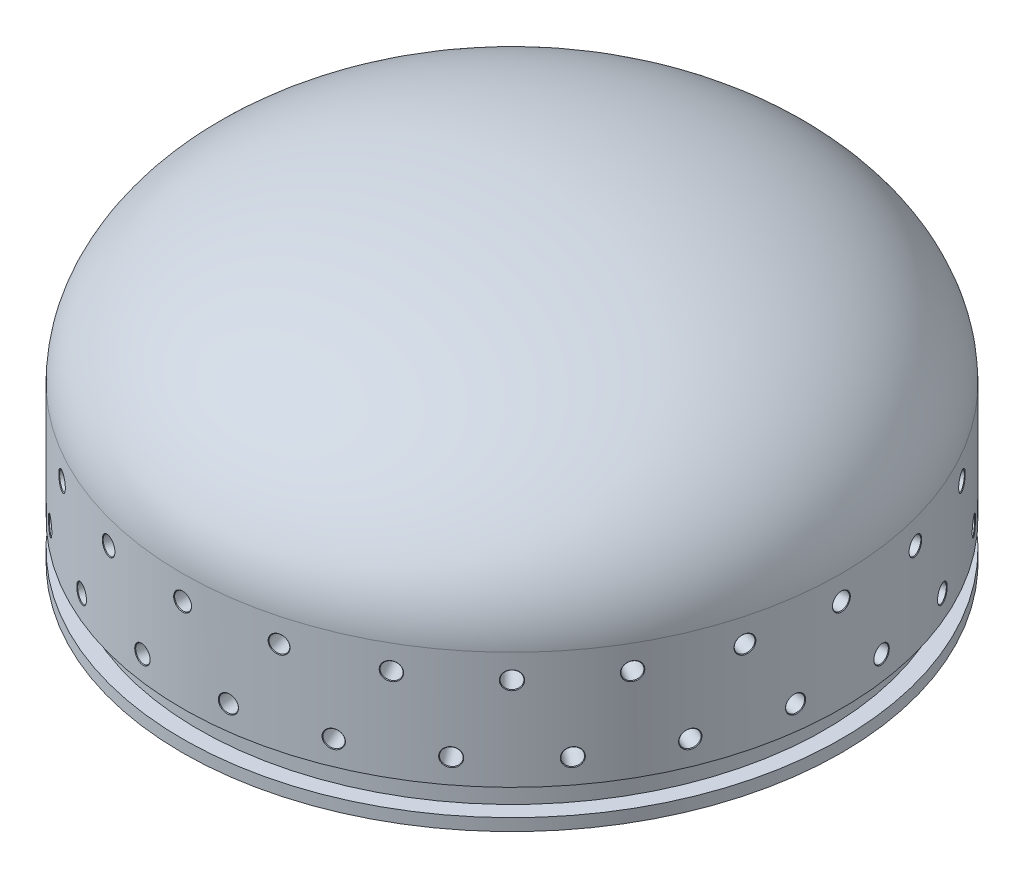
SolidWorks part; units mm, degrees
material "AW-6082-T6 (PA4)"
ref_plane "Płaszczyzna przednia" through (0, 0, 0) normal (0, 0, 1) x (1, 0, 0)
ref_plane "Płaszczyzna górna" through (0, 0, 0) normal (0, 1, 0) x (1, 0, 0)
ref_plane "Płaszczyzna prawa" through (0, 0, 0) normal (1, 0, 0) x (0, 0, -1)
sketch "Szkic1" plane through (0, 0, 0) normal (0, 1, 0) x (1, 0, 0)
  circle A0 centre (0, 0) radius 81.7
  dimension "D1" = 163.4
extrude "Dodanie-wyciągnięcie1" add sketch "Szkic1" along normal blind 38.5
ref_plane "Płaszczyzna1" through (0, 0, -81.7) normal (0, 0, -1) x (-1, 0, 0)
ref_plane "Płaszczyzna2" through (10.664, 0, -81.001) normal (0.1305, 0, -0.9914) x (0, -1, 0)
hole_wizard "Otwór gwintowany M51" positions "Szkic2" profile "Szkic3" hole size "M5" standard "ISO"
sketch "Szkic2" plane through (0, 0, -81.7) normal (0, 0, -1) x (-1, 0, 0)
  line L0 (81.7, 0) -> (81.7, 38.5) construction
  line L1 (-81.7, 38.5) -> (-81.7, 0) construction
  line L2 (81.7, 0) -> (81.7, 38.5)
  line L3 (-81.7, 38.5) -> (-81.7, 0)
  line L4 (0, 51.4702) -> (0, -13.4001) construction
  line L5 (81.7, 38.5) -> (-81.7, 38.5) construction
  point P11 (0, 32.5)
  dimension "D1" = 6
sketch "Szkic3" plane through (0, 32.5, -81.7) normal (1, 0, 0) x (0, 1, 0)
  line L0 (0, 0) -> (0, 9.2618)
  line L1 (0, 9.2618) -> (2.1, 8)
  line L2 (2.1, 8) -> (2.1, 0.15)
  line L3 (2.1, 0.15) -> (2.25, 0)
  line L5 (2.25, 0) -> (0, 0)
  line L6 (-2.1, 0.15) -> (-2.25, 0) construction
  line L10 (0, 9.2618) -> (-2.1, 8) construction
  line L11 (0, -6.35) -> (0, 107.95) construction
  dimension "Średnica otworu" = 4.2
  dimension "Głębokośc otworu" = 8
  dimension "Średnica zewnętrznego pogłębienia stożkowego" = 4.5
  dimension "Kąt zewnętrznego pogłębienia stożkowego" = 90
  dimension "Kąt wiertła" = 118
hole_wizard "Otwór gwintowany M52" positions "Szkic6" profile "Szkic7" hole size "M5" standard "ISO"
sketch "Szkic6" plane through (10.664, 0, -81.001) normal (0.1305, 0, -0.9914) x (0, -1, 0)
  line L0 (-38.5, -81.7) -> (0, -81.7) construction
  line L1 (0, 81.7) -> (-38.5, 81.7) construction
  line L2 (-38.5, -81.7) -> (0, -81.7)
  line L3 (0, 81.7) -> (-38.5, 81.7)
  line L4 (-54.6249, 0) -> (16.9218, 0) construction
  ellipse E0 centre (-32.5, 10.6444) end of major axis (-30.4, 10.6444) minor radius 2.082 construction
  point P10 (-15.5, 0)
  dimension "D1" = 17
sketch "Szkic7" plane through (10.664, 15.5, -81.001) normal (0, 1, 0) x (-0.9914, 0, -0.1305)
  line L0 (0, 0) -> (0, 9.2618)
  line L1 (0, 9.2618) -> (2.1, 8)
  line L2 (2.1, 8) -> (2.1, 0.15)
  line L3 (2.1, 0.15) -> (2.25, 0)
  line L5 (2.25, 0) -> (0, 0)
  line L6 (-2.1, 0.15) -> (-2.25, 0) construction
  line L10 (0, 9.2618) -> (-2.1, 8) construction
  line L11 (0, -6.35) -> (0, 107.95) construction
  dimension "Średnica otworu" = 4.2
  dimension "Głębokośc otworu" = 8
  dimension "Średnica zewnętrznego pogłębienia stożkowego" = 4.5
  dimension "Kąt zewnętrznego pogłębienia stożkowego" = 90
  dimension "Kąt wiertła" = 118
pattern_circular "Szyk kołowy1" count 24 over 360 about axis through (0, 38.5, 0) along (0, -1, 0) of "Otwór gwintowany M51", "Otwór gwintowany M52"
sketch "Szkic8" plane through (0, 0, 0) normal (0, 0, 1) x (1, 0, 0)
  line L0 (-81.7, 30.25) -> (-81.7, 0) construction
  line L1 (-81.7, 30.25) -> (-81.7, 0)
  line L2 (-81.7, 0) -> (81.7, 0) construction
  line L3 (-81.7, 9.5) -> (-77.7, 9.5)
  line L4 (-81.7, 9.5) -> (-81.7, 3)
  line L5 (-81.7, 3) -> (-77.7, 3)
  line L6 (-77.7, 9.5) -> (-77.7, 3)
  line L8 (0, 56.0732) -> (0, -20.5484) construction
  line L9 (81.7, 0) -> (81.7, 30.25) construction
  dimension "D1" = 4
  dimension "D2" = 6.5
  dimension "D3" = 3
revolve "Wycięcie-obrót1" cut sketch "Szkic8" angle 360 about L8 region at (-79.7, 6.25, 0)
sketch "Szkic9" plane through (0, 0, 0) normal (0, 0, 1) x (1, 0, 0)
  line L0 (0, -10.2266) -> (0, 51.1756) construction
  line L1 (-81.7, 0) -> (81.7, 0) construction
  line L2 (0, 0) -> (-66.7, 0)
  line L3 (0, 0) -> (0, 23.5)
  line L4 (0, 23.5) -> (-66.7, 23.5)
  line L5 (-66.7, 0) -> (-66.7, 23.5)
  line L6 (-81.7, 30.2501) -> (-81.7, 9.5) construction
  line L7 (-81.7, 30.2501) -> (-81.7, 9.5)
  line L8 (-73.7, 34.6) -> (-73.7, 30.4) construction
  line L9 (81.7, 38.5) -> (-81.7, 38.5) construction
  line L10 (81.7, 38.5) -> (-81.7, 38.5)
  dimension "D1" = 15
  dimension "D2" = 7
  dimension "D3" = 15
revolve "Wycięcie-obrót2" cut sketch "Szkic9" angle 360 about L0 region at (-33.35, 11.75, 0)
sketch "Szkic10" plane through (0, 23.5, 0) normal (0, -1, 0) x (1, 0, 0)
  circle A1 centre (0, 0) radius 66.7
  circle A2 centre (0, 0) radius 66.7
  dimension "D1" = 0
extrude "Wytnij-wyciągnięcie1" cut sketch "Szkic10" against normal through all
sketch "Szkic11" plane through (0, 0, 0) normal (0, 0, 1) x (1, 0, 0)
  line L0 (0, 38.5) -> (0, 98.1331) construction
  line L1 (66.7, 38.5) -> (-66.7, 38.5) construction
  line L2 (0, 38.5) -> (-66.7, 38.5) construction
  line L4 (66.7, 38.5) -> (81.7, 38.5)
  line L5 (0, 82) -> (0, 71)
  ellipse E0 centre (0, 38.5) end of major axis (66.7, 38.5) minor radius 32.5 (66.7, 38.5) -> (0, 71) ccw
  ellipse E1 centre (0, 38.5) end of major axis (-81.7, 38.5) minor radius 43.5 (81.7, 38.5) -> (0, 82) ccw
  point P18 (66.7, 38.5)
  dimension "D1" = 43.5
  dimension "D2" = 11
revolve "Obrót3" add sketch "Szkic11" angle 360 about L0
